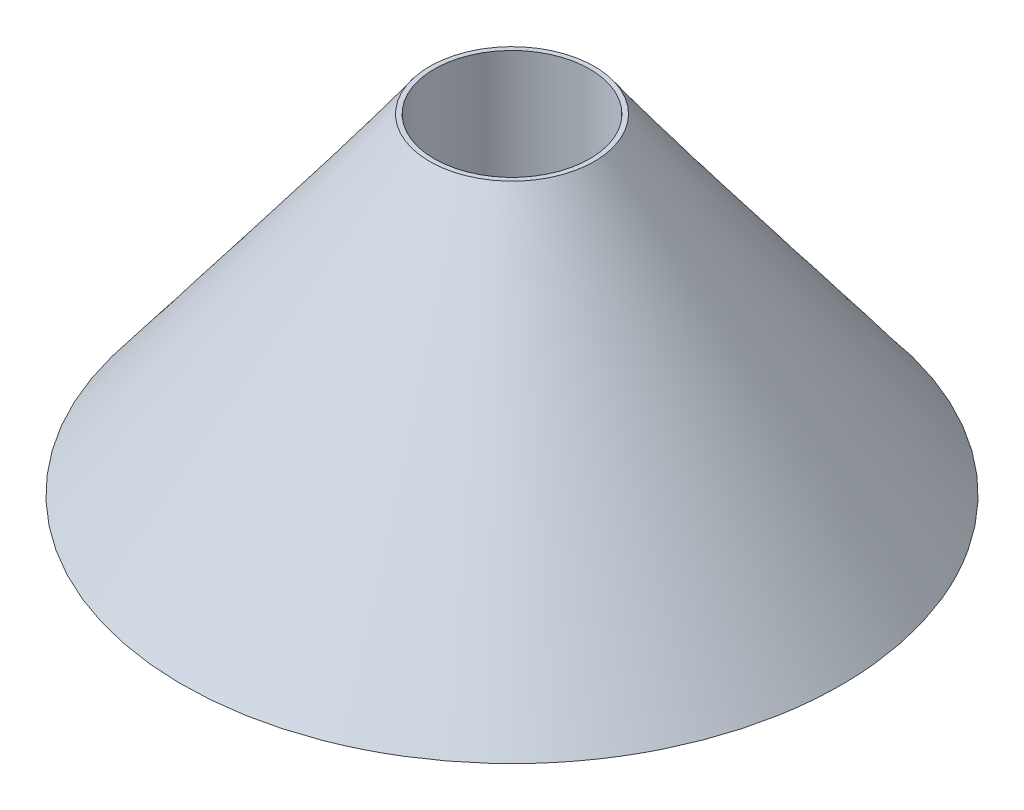
SolidWorks part; units mm, degrees
material "ABS"
ref_plane "Front Plane" through (0, 0, 0) normal (0, 0, 1) x (1, 0, 0)
ref_plane "Top Plane" through (0, 0, 0) normal (0, 1, 0) x (1, 0, 0)
ref_plane "Right Plane" through (0, 0, 0) normal (1, 0, 0) x (0, 0, -1)
ref_axis "X" through (-88.99, 0, 0) along (1, 0, 0)
ref_axis "Y" through (0, 55, 0) along (0, -1, 0)
ref_axis "Z" through (0, 0, -88.99) along (0, 0, 1)
sketch "Sketch1" plane through (0, 0, 0) normal (0, 1, 0) x (1, 0, 0)
  circle A0 centre (0, 0) radius 4
  dimension "D1" = 8
ref_plane "Plane1" through (0, 4, 0) normal (0, 1, 0) x (1, 0, 0)
sketch "Sketch2" plane through (0, 4, 0) normal (0, 1, 0) x (1, 0, 0)
  circle A0 centre (0, 0) radius 1
  dimension "D1" = 2
loft "Loft1" add profiles "Sketch1", "Sketch2" connector at (-3.8011, 0, -1.2456) connector at (-0.8008, 4, -0.5989)
sketch "Sketch4" plane through (0, 4, 0) normal (0, 1, 0) x (1, 0, 0)
  circle A0 centre (0, 0) radius 0.9438
  circle A2 centre (0, 0) radius 0.7938 construction
  dimension "D1" = 0.15
extrude "Cut-Extrude1" cut sketch "Sketch4" against normal blind 2
